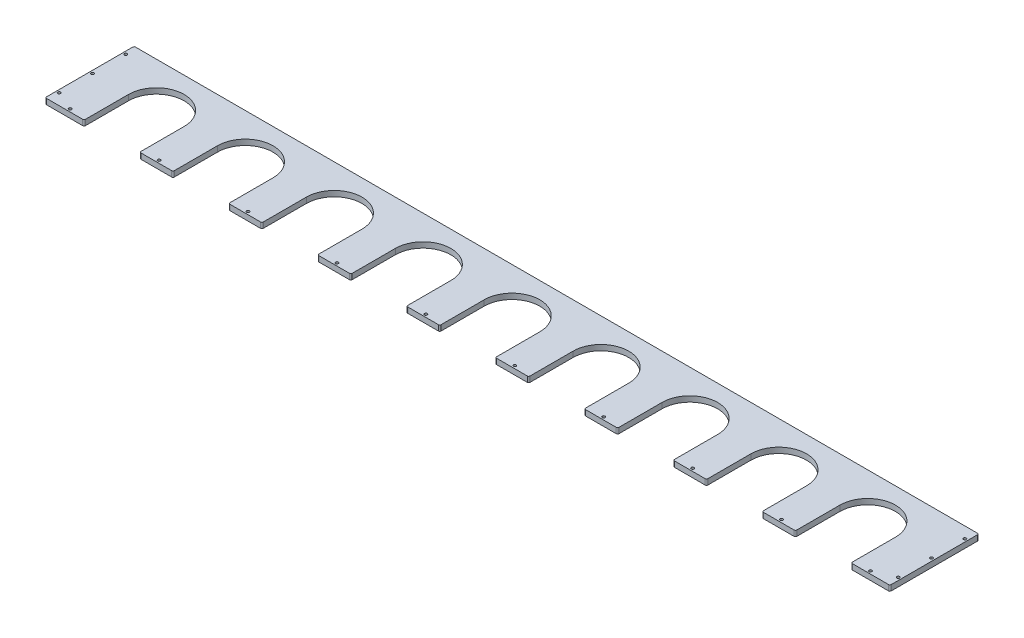
SolidWorks part; units mm, degrees
material "PC High Viscosity"
ref_plane "Front Plane" through (0, 0, 0) normal (0, 0, 1) x (1, 0, 0)
ref_plane "Top Plane" through (0, 0, 0) normal (0, 1, 0) x (1, 0, 0)
ref_plane "Right Plane" through (0, 0, 0) normal (1, 0, 0) x (0, 0, -1)
sketch "Sketch1" plane through (0, 0, 0) normal (0, 1, 0) x (1, 0, 0)
  line L1 (-965.2, 101.6) -> (965.2, 101.6)
  line L2 (-965.2, 101.6) -> (-965.2, -101.6)
  line L4 (965.2, 101.6) -> (965.2, -101.6)
  line L5 (-965.2, 101.6) -> (965.2, -101.6) construction
  line L6 (-965.2, -101.6) -> (965.2, 101.6) construction
  line L8 (-965.2, -101.6) -> (965.2, -101.6)
  point P0 (0, 0)
  dimension "D1" = 1930.4
  dimension "D2" = 203.2
extrude "Boss-Extrude1" add sketch "Sketch1" along normal blind 12.7
sketch "Sketch2" plane through (0, 12.7, 0) normal (0, 1, 0) x (1, 0, 0)
  line L0 (-876.3, 0) -> (-876.3, -101.6)
  line L1 (-965.2, -101.6) -> (965.2, -101.6) construction
  line L2 (-876.3, -101.6) -> (-749.3, -101.6)
  line L3 (-749.3, -101.6) -> (-749.3, 0)
  line L5 (-673.1, 0) -> (-673.1, -101.6)
  line L6 (-673.1, -101.6) -> (-546.1, -101.6)
  line L7 (-546.1, -101.6) -> (-546.1, 0)
  line L8 (-469.9, 0) -> (-469.9, -101.6)
  line L9 (-469.9, -101.6) -> (-342.9, -101.6)
  line L10 (-342.9, -101.6) -> (-342.9, 0)
  line L11 (-266.7, 0) -> (-266.7, -101.6)
  line L12 (-266.7, -101.6) -> (-139.7, -101.6)
  line L13 (-139.7, -101.6) -> (-139.7, 0)
  line L14 (-63.5, 0) -> (-63.5, -101.6)
  line L15 (-63.5, -101.6) -> (63.5, -101.6)
  line L16 (63.5, -101.6) -> (63.5, 0)
  line L17 (139.7, 0) -> (139.7, -101.6)
  line L18 (139.7, -101.6) -> (266.7, -101.6)
  line L19 (266.7, -101.6) -> (266.7, 0)
  line L20 (342.9, 0) -> (342.9, -101.6)
  line L21 (342.9, -101.6) -> (469.9, -101.6)
  line L22 (469.9, -101.6) -> (469.9, 0)
  line L23 (546.1, 0) -> (546.1, -101.6)
  line L24 (546.1, -101.6) -> (673.1, -101.6)
  line L25 (673.1, -101.6) -> (673.1, 0)
  line L26 (749.3, 0) -> (749.3, -101.6)
  line L27 (749.3, -101.6) -> (876.3, -101.6)
  line L28 (876.3, -101.6) -> (876.3, 0)
  arc A0 (-749.3, 0) -> (-876.3, 0) centre (-812.8, 0) ccw
  arc A1 (-546.1, 0) -> (-673.1, 0) centre (-609.6, 0) ccw
  arc A2 (-342.9, 0) -> (-469.9, 0) centre (-406.4, 0) ccw
  arc A3 (-139.7, 0) -> (-266.7, 0) centre (-203.2, 0) ccw
  arc A4 (63.5, 0) -> (-63.5, 0) centre (0, 0) ccw
  arc A5 (266.7, 0) -> (139.7, 0) centre (203.2, 0) ccw
  arc A6 (469.9, 0) -> (342.9, 0) centre (406.4, 0) ccw
  arc A7 (673.1, 0) -> (546.1, 0) centre (609.6, 0) ccw
  arc A8 (876.3, 0) -> (749.3, 0) centre (812.8, 0) ccw
  dimension "D1" = 63.5
  dimension "D2" = 101.6
  dimension "D5" = 76.2
  dimension "D4" = 9
extrude "Cut-Extrude1" cut sketch "Sketch2" against normal through all
fillet "Fillet1" radius 3.175 22 edges at (965.2, 6.35, -101.6) (965.2, 6.35, 101.6) (876.3, 6.35, 101.6) (749.3, 6.35, 101.6) (673.1, 6.35, 101.6) (546.1, 6.35, 101.6) (469.9, 6.35, 101.6) (342.9, 6.35, 101.6) (266.7, 6.35, 101.6) (139.7, 6.35, 101.6) (63.5, 6.35, 101.6) (-63.5, 6.35, 101.6) (-139.7, 6.35, 101.6) (-266.7, 6.35, 101.6) (-342.9, 6.35, 101.6) (-469.9, 6.35, 101.6) (-546.1, 6.35, 101.6) (-749.3, 6.35, 101.6) (-673.1, 6.35, 101.6) (-876.3, 6.35, 101.6) (-965.2, 6.35, 101.6) (-965.2, 6.35, -101.6)
hole_wizard "1/4 (0.25) Diameter Hole1" positions "Sketch3" profile "Sketch4" hole size "1/4" standard "ANSI Inch" end condition through all
sketch "Sketch3" plane through (0, 12.7, 0) normal (0, 1, 0) x (1, 0, 0)
  line L0 (-958.85, 76.2) -> (-958.85, 0) construction
  line L1 (-958.85, 0) -> (-958.85, -76.2) construction
  line L3 (958.85, 76.2) -> (958.85, 0) construction
  line L4 (958.85, 0) -> (958.85, -76.2) construction
  line L6 (-965.2, 98.425) -> (-965.2, -98.425) construction
  line L7 (965.2, -98.425) -> (965.2, 98.425) construction
  line L8 (-914.4, -95.25) -> (914.4, -95.25) construction
  line L10 (-962.025, -101.6) -> (-879.475, -101.6) construction
  point P0 (-958.85, 76.2)
  point P2 (-958.85, 0)
  point P4 (-958.85, -76.2)
  point P6 (958.85, -76.2)
  point P8 (958.85, 0)
  point P10 (958.85, 76.2)
  point P36 (-914.4, -95.25)
  point P37 (-711.2, -95.25)
  point P39 (-508, -95.25)
  point P41 (-304.8, -95.25)
  point P43 (-101.6, -95.25)
  point P45 (101.6, -95.25)
  point P47 (304.8, -95.25)
  point P49 (508, -95.25)
  point P51 (711.2, -95.25)
  point P56 (914.4, -95.25)
  dimension "D1" = 76.2
  dimension "D2" = 6.35
  dimension "D3" = 6.35
  dimension "D4" = 50.8
  dimension "D5" = 50.8
  dimension "D6" = 6.35
  dimension "D7" = 203.2
  dimension "D8" = 203.2
  dimension "D9" = 203.2
  dimension "D10" = 203.2
  dimension "D11" = 203.2
  dimension "D12" = 203.2
  dimension "D13" = 203.2
  dimension "D14" = 203.2
sketch "Sketch4" plane through (-958.85, 12.7, -76.2) normal (1, 0, 0) x (0, 0, 1)
  line L0 (0, 0) -> (0, 12.7)
  line L1 (0, 12.7) -> (3.175, 12.7)
  line L2 (3.175, 12.7) -> (3.175, 0)
  line L5 (3.175, 0) -> (0, 0)
  line L11 (0, -6.35) -> (0, 107.95) construction
  dimension "Thru Hole Dia." = 6.35
  dimension "Thru Hole Depth" = 12.7
